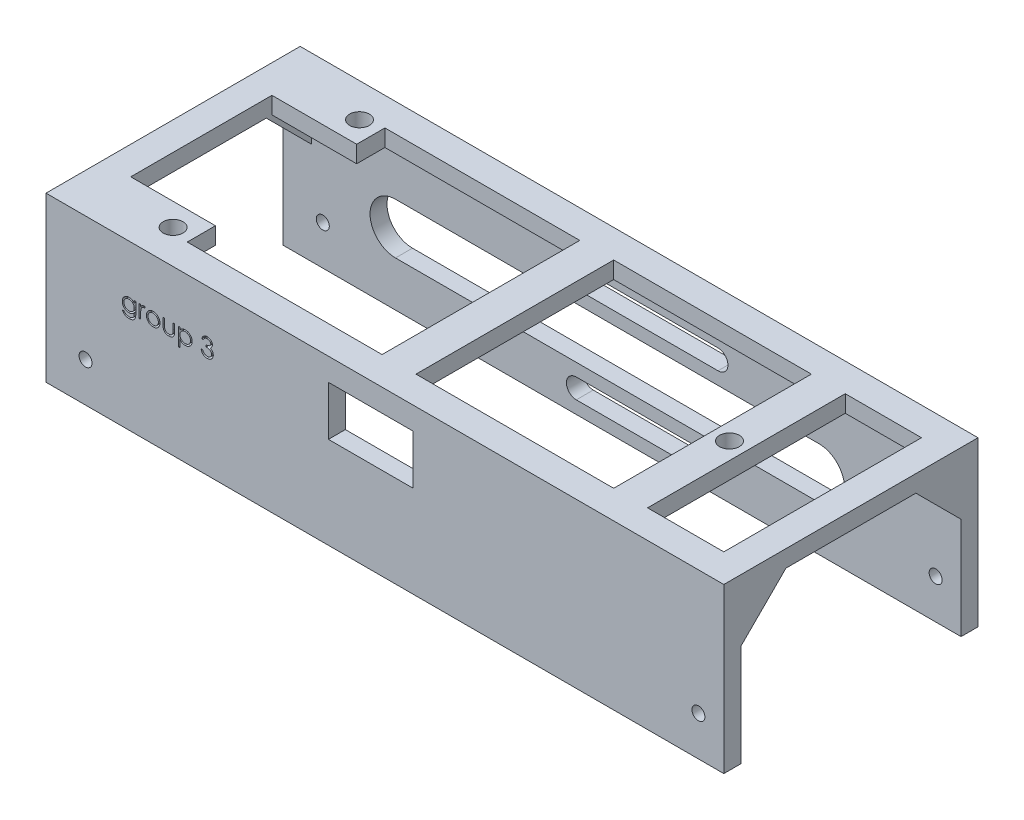
SolidWorks part; units mm, degrees
other "Markup1"
sketch "Sketch23" plane through (120, 29, 45) normal (0.0467, 0.9512, 0.3049) x (0.9885, 0, -0.1514)
sketch "Sketch24" plane through (120, 29, 45) normal (0.0467, 0.9512, 0.3049) x (0.9885, 0, -0.1514)
sketch "Sketch25" plane through (120, 29, 45) normal (0.0467, 0.9512, 0.3049) x (0.9885, 0, -0.1514)
ref_plane "Front Plane" through (0, 0, 0) normal (0, 0, 1) x (1, 0, 0)
ref_plane "Top Plane" through (0, 0, 0) normal (0, 1, 0) x (1, 0, 0)
ref_plane "Right Plane" through (0, 0, 0) normal (1, 0, 0) x (0, 0, -1)
sketch "Sketch1" plane through (0, 0, 0) normal (0, 0, 1) x (1, 0, 0)
  line L9 (21.172, -17.9478) -> (91.172, -17.9478)
  line L10 (21.172, -17.9478) -> (21.172, -40.3878)
  line L11 (4, -8) -> (200.227, -8) construction
  line L12 (4, -8) -> (-67.5185, -8) construction
  line L13 (21.172, -40.3878) -> (91.172, -40.3878)
  line L14 (91.172, -17.9478) -> (91.172, -40.3878)
  line L15 (0, 0) -> (120, 0)
  line L16 (0, 0) -> (0, 29)
  line L17 (0, 29) -> (120, 29)
  line L18 (120, 0) -> (120, 29)
  circle A0 centre (4, 7) radius 1.15
  circle A1 centre (4, 7) radius 15 construction
  circle A3 centre (77.172, -29.1678) radius 3.6067
  circle A4 centre (116, 7) radius 15 construction
  circle A5 centre (116, 7) radius 1.15
  point P19 (21.172, -29.1678)
  dimension "D4" = 30
  dimension "D2" = 14
  dimension "D7" = 30
  dimension "D11" = 4
  dimension "D13" = 2.3
  dimension "D14" = 2.3
  dimension "D3" = 70
  dimension "D5" = 22.44
  dimension "D6" = 120
  dimension "D8" = 29
  dimension "D9" = 4
  dimension "D10" = 7
  dimension "D12" = 7
extrude "Boss-Extrude5" add sketch "Sketch1" along normal blind 45 contours L16 L15 L18 L17
shell "Shell9" thickness 3 removed face at (120, 14.5, 22.5) removed face at (60, 0, 22.5) removed face at (0, 14.5, 22.5)
sketch "Sketch3" plane through (0, 0, 0) normal (0, 0, -1) x (-1, 0, 0)
  line L0 (0, 0) -> (-120, 0) construction
  line L1 (-120, 0) -> (-120, 29) construction
  line L2 (0, 0) -> (0, 29) construction
  circle A0 centre (-7, 7) radius 1.15
  circle A1 centre (-115.5, 7) radius 1.15
  dimension "D1" = 2.3
  dimension "D2" = 2.3
  dimension "D3" = 7
  dimension "D4" = 4.5
  dimension "D5" = 7
  dimension "D6" = 7
extrude "Cut-Extrude2" cut sketch "Sketch3" against normal blind 79
sketch "Sketch6" plane through (0, 0, 0) normal (0, 0, -1) x (-1, 0, 0)
  line L0 (-76.9735, 21) -> (-51.8835, 21) construction
  line L1 (-76.9735, 22.75) -> (-51.8835, 22.75)
  line L2 (-76.9735, 19.25) -> (-51.8835, 19.25)
  line L7 (41.5249, -18.7743) -> (41.5249, -41.2143) construction
  line L8 (-94.8735, 12.5) -> (-19.8735, 12.5) construction
  line L9 (-94.8735, 17) -> (-19.8735, 17)
  line L10 (-94.8735, 8) -> (-19.8735, 8)
  line L11 (-19.8735, 12.5) -> (-17.326, 12.5) construction
  line L12 (-76.9735, 4) -> (-51.8835, 4) construction
  line L13 (-76.9735, 2.25) -> (-51.8835, 2.25)
  line L14 (-76.9735, 5.75) -> (-51.8835, 5.75)
  line L15 (4.7849, -29.9943) -> (74.7849, -29.9943) construction
  line L20 (4.7849, -18.7743) -> (74.7849, -18.7743)
  line L21 (4.7849, -18.7743) -> (4.7849, -41.2143)
  line L22 (4.7849, -41.2143) -> (74.7849, -41.2143)
  line L23 (74.7849, -18.7743) -> (74.7849, -41.2143)
  line L24 (-120, 0) -> (-120, 29) construction
  line L25 (63.3749, -18.7743) -> (63.3749, -41.2143) construction
  line L26 (0, 29) -> (-120, 29) construction
  arc A4 (-94.8735, 17) -> (-94.8735, 8) centre (-94.8735, 12.5) ccw
  arc A5 (-76.9735, 22.75) -> (-76.9735, 19.25) centre (-76.9735, 21) ccw
  arc A6 (-51.8835, 19.25) -> (-51.8835, 22.75) centre (-51.8835, 21) ccw
  arc A7 (-19.8735, 8) -> (-19.8735, 17) centre (-19.8735, 12.5) ccw
  arc A8 (-76.9735, 2.25) -> (-76.9735, 5.75) centre (-76.9735, 4) cw
  arc A9 (-51.8835, 5.75) -> (-51.8835, 2.25) centre (-51.8835, 4) cw
  circle A15 centre (16.1349, -29.9943) radius 1.5
  circle A16 centre (36.3249, -21.4943) radius 1.5
  circle A17 centre (36.3249, -38.4943) radius 1.5
  circle A18 centre (36.3249, -38.4943) radius 1.5
  circle A19 centre (27.0349, -29.9943) radius 2.3201
  point P11 (-64.4285, 21)
  point P19 (-57.3735, 12.5)
  point P31 (-64.4285, 4)
  dimension "D8" = 1.75
  dimension "D13" = 4.5
  dimension "D10" = 3
  dimension "D14" = 3
  dimension "D9" = 25.09
  dimension "D2" = 8.5
  dimension "D3" = 17.9
  dimension "D4" = 70
  dimension "D5" = 22.44
  dimension "D6" = 36.74
  dimension "D7" = 11.35
  dimension "D11" = 5.2
  dimension "D12" = 8.5
  dimension "D15" = 22.25
  dimension "D16" = 75
  dimension "D17" = 25.1265
  dimension "D18" = 11.41
  dimension "D19" = 16.5
extrude "Cut-Extrude8" cut sketch "Sketch6" against normal blind 23 contours L10 A7 L9 | L2 A6 L1 A5 | L13 A9 L14 A8 region at (64.4285, 21, 0) region at (57.3735, 12.5, 0)
sketch "Sketch7" plane through (0, 0, 45) normal (0, 0, 1) x (1, 0, 0)
  line L1 (50, 25) -> (65, 25)
  line L2 (50, 25) -> (50, 16.25)
  line L3 (50, 16.25) -> (65, 16.25)
  line L4 (65, 25) -> (65, 16.25)
  line L5 (0, 0) -> (120, 0) construction
  line L7 (0, 0) -> (0, 29) construction
  dimension "D1" = 50
  dimension "D2" = 15
  dimension "D3" = 8.75
  dimension "D4" = 25
extrude "Cut-Extrude9" cut sketch "Sketch7" against normal blind 20
sketch "Sketch13" plane through (0, 29, 0) normal (0, 1, 0) x (1, 0, 0)
  line L1 (0, 0) -> (120, 0) construction
  line L4 (5, -5) -> (115, -5)
  line L5 (5, -5) -> (5, -40)
  line L6 (5, -40) -> (115, -40)
  line L8 (0, -45) -> (0, 0) construction
  line L16 (115, -5) -> (115, -40)
  line L17 (120, -45) -> (120, 0) construction
  dimension "D1" = 5
  dimension "D2" = 5
  dimension "D5" = 5
  dimension "D6" = 35
extrude "Cut-Extrude14" cut sketch "Sketch13" against normal blind 10
sketch "Sketch17" plane through (0, 29, 0) normal (0, 1, 0) x (1, 0, 0)
  line L0 (0, -22.5) -> (120, -22.5) construction
  line L1 (5, -5) -> (20, -5)
  line L2 (5, -5) -> (5, -10)
  line L3 (5, -10) -> (20, -10)
  line L4 (20, -5) -> (20, -10)
  line L5 (5, -40) -> (20, -40)
  line L6 (5, -40) -> (5, -35)
  line L7 (5, -35) -> (20, -35)
  line L8 (20, -40) -> (20, -35)
  line L17 (0, -45) -> (0, 0) construction
  line L18 (120, -45) -> (120, 0) construction
  line L25 (115, -5) -> (5, -5) construction
  line L26 (95.5, -5) -> (101.5, -5)
  line L27 (95.5, -5) -> (95.5, -40)
  line L28 (95.5, -40) -> (101.5, -40)
  line L29 (101.5, -5) -> (101.5, -40)
  line L30 (5, -40) -> (115, -40) construction
  line L32 (54.5, -5) -> (60.5, -5)
  line L33 (54.5, -5) -> (54.5, -40)
  line L34 (54.5, -40) -> (60.5, -40)
  line L35 (60.5, -5) -> (60.5, -40)
  circle A0 centre (16.5, -39) radius 1.75
  circle A1 centre (16.5, -6) radius 1.75
  circle A2 centre (98.5, -22.5) radius 1.75
  point P41 (98.5, -5)
  line M10 (5, -40) -> (5, -5)
  line M11 (5, -5) -> (115, -5)
  line M13 (115, -40) -> (5, -40)
  dimension "D3" = 3.5
  dimension "D6" = 3.5
  dimension "D11" = 33
  dimension "D12" = 16.5
  dimension "D13" = 3.5
  dimension "D1" = 5
  dimension "D2" = 15
  dimension "D4" = 5
  dimension "D5" = 15
  dimension "D7" = 6
  dimension "D8" = 18.5
  dimension "D9" = 6
  dimension "D10" = 35
extrude "Boss-Extrude6" add sketch "Sketch17" against normal blind 3 contours A1 L3 L4 M11 M10 | L1 A1 | A0 L8 L7 M13 M10 | L5 A0 | L33 L32 L35 L34 | L27 L26 L29 L28 region at (12.0151, 29, 7.6523) region at (16.5, 29, 6.2435) region at (12.0151, 29, 37.3477) region at (16.5, 29, 38.7565)
extrude "Cut-Extrude16" cut sketch "Sketch17<4>" against normal blind 10 contours A2 L0 | L0 A2 | L1 A1 | L1 A1 | L5 A0 | L5 A0 | A2 region at (98.5, 29, 21.7573) region at (98.5, 29, 23.2427) region at (16.5, 29, 4.6937) region at (16.5, 29, 6.2435) region at (16.5, 29, 38.7565) region at (16.5, 29, 40.3063)
sketch "Sketch17<4>" plane through (0, 29, 0) normal (0, 1, 0) x (1, 0, 0) same geometry as "Sketch17"
sketch "Sketch20" plane through (0, 0, 45) normal (0, 0, 1) x (1, 0, 0)
  line L0 (13.2558, 18.0126) -> (38.9246, 18.0126) construction
  text T0 "group 3"
extrude "Cut-Extrude15" cut sketch "Sketch20" against normal blind 1.5
sketch "Sketch21" plane through (0, 0, 0) normal (-1, 0, 0) x (0, 0, 1)
  line L0 (3, 26) -> (3, 18)
  line L1 (3, 0) -> (3, 26) construction
  line L2 (3, 18) -> (11, 26)
  line L3 (42, 26) -> (3, 26) construction
  line L4 (11, 26) -> (3, 26)
  line L5 (42, 26) -> (34, 26)
  line L6 (34, 26) -> (42, 18)
  line L7 (42, 0) -> (42, 26) construction
  line L8 (42, 18) -> (42, 26)
  dimension "D1" = 8
  dimension "D2" = 8
  dimension "D3" = 8
  dimension "D4" = 8
extrude "Boss-Extrude7" add sketch "Sketch21" against normal blind 5
sketch "Sketch22" plane through (120, 0, 0) normal (1, 0, 0) x (0, 0, -1)
  line L0 (-42, 26) -> (-42, 18)
  line L1 (-42, 18) -> (-34, 26)
  line L2 (-34, 26) -> (-42, 26)
  line L3 (-11, 26) -> (-3, 26)
  line L4 (-3, 26) -> (-3, 18)
  line L5 (-3, 18) -> (-11, 26)
extrude "Boss-Extrude8" add sketch "Sketch22" against normal blind 5
equation "\"slot­_width\"=25.09"
equation "\"D9@Sketch6\"=\"slot­_width\""
